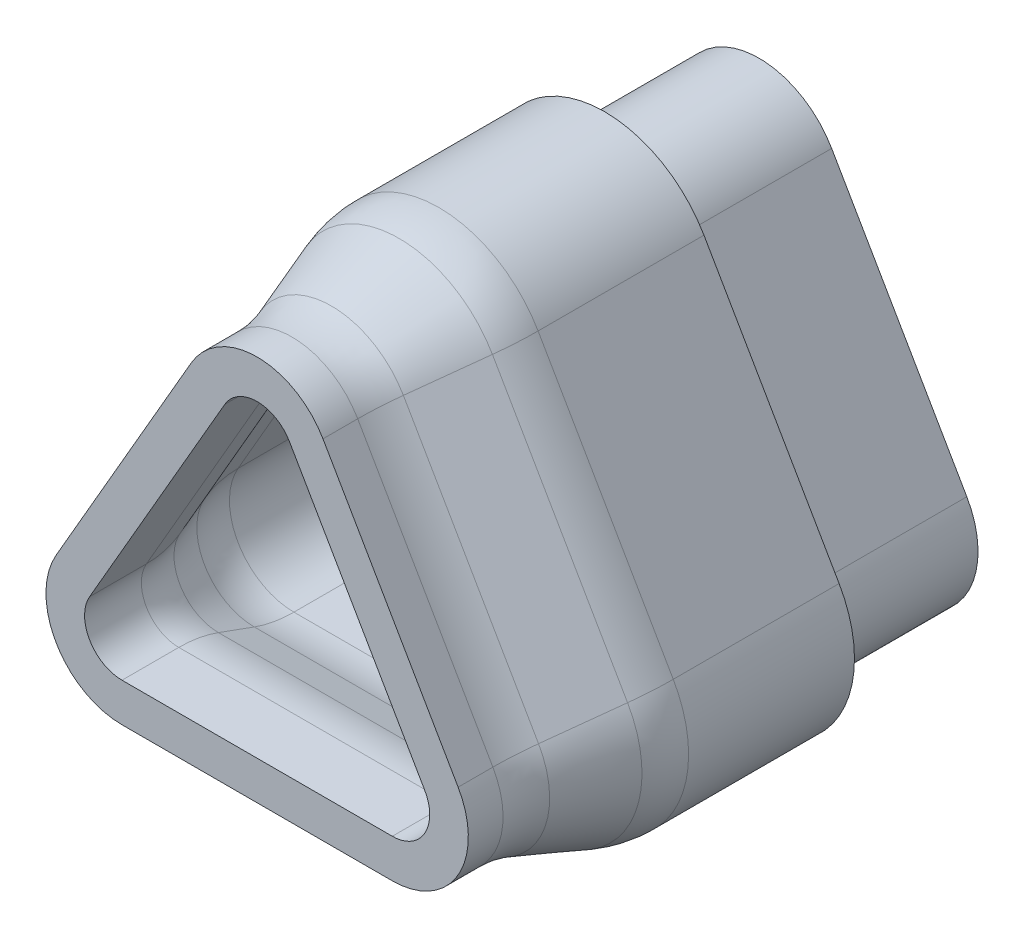
SolidWorks part; units mm, degrees
ref_plane "Спереди" through (0, 0, 0) normal (0, 0, 1) x (1, 0, 0)
ref_plane "Сверху" through (0, 0, 0) normal (0, 1, 0) x (1, 0, 0)
ref_plane "Справа" through (0, 0, 0) normal (1, 0, 0) x (0, 0, -1)
sketch "Эскиз2" plane through (0, 0, -4) normal (0, 0, 1) x (1, 0, 0)
  line L0 (-1.4453, 9.8655) -> (-4.9453, 3.8034)
  line L1 (-3.5, 1.3) -> (3.5, 1.3)
  line L2 (4.9453, 3.8034) -> (1.4453, 9.8655)
  line L3 (5.3783, 4.0534) -> (1.8783, 10.1155)
  line L4 (-1.8783, 10.1155) -> (-5.3783, 4.0534)
  line L5 (-3.5, 0.8) -> (3.5, 0.8)
  line L6 (5.3783, 4.0534) -> (1.8783, 10.1155)
  line L7 (-1.8783, 10.1155) -> (-5.3783, 4.0534)
  line L8 (-3.5, 0.8) -> (3.5, 0.8)
  arc A0 (1.4453, 9.8655) -> (-1.4453, 9.8655) centre (0, 9.0311) ccw
  arc A1 (-4.9453, 3.8034) -> (-3.5, 1.3) centre (-3.5, 2.9689) ccw
  arc A2 (3.5, 1.3) -> (4.9453, 3.8034) centre (3.5, 2.9689) ccw
  arc A3 (3.5, 0.8) -> (5.3783, 4.0534) centre (3.5, 2.9689) ccw
  arc A4 (1.8783, 10.1155) -> (-1.8783, 10.1155) centre (0, 9.0311) ccw
  arc A5 (-5.3783, 4.0534) -> (-3.5, 0.8) centre (-3.5, 2.9689) ccw
  arc A6 (3.5, 0.8) -> (5.3783, 4.0534) centre (3.5, 2.9689) ccw
  arc A7 (1.8783, 10.1155) -> (-1.8783, 10.1155) centre (0, 9.0311) ccw
  arc A8 (-5.3783, 4.0534) -> (-3.5, 0.8) centre (-3.5, 2.9689) ccw
  dimension "D1" = 0
  dimension "D2" = 0.5
extrude "Бобышка-Вытянуть1" add sketch "Эскиз2" along normal up to surface (4 mm away)
sketch "Эскиз3" plane through (0, 0, 0) normal (0, 0, 1) x (1, 0, 0)
  line L0 (4.9453, 3.8034) -> (1.4453, 9.8655) construction
  line L1 (-1.4453, 9.8655) -> (-4.9453, 3.8034) construction
  line L2 (-3.5, 1.3) -> (3.5, 1.3) construction
  line L3 (-3.5, 0) -> (3.5, 0)
  line L4 (6.0712, 4.4534) -> (2.5712, 10.5155)
  line L5 (-2.5712, 10.5155) -> (-6.0712, 4.4534)
  line L6 (-3.5, 0) -> (3.5, 0)
  line L7 (6.0712, 4.4534) -> (2.5712, 10.5155)
  line L8 (-2.5712, 10.5155) -> (-6.0712, 4.4534)
  line L9 (4.9453, 3.8034) -> (1.4453, 9.8655)
  line L10 (-1.4453, 9.8655) -> (-4.9453, 3.8034)
  line L11 (-3.5, 1.3) -> (3.5, 1.3)
  arc A0 (1.4453, 9.8655) -> (-1.4453, 9.8655) centre (0, 9.0311) ccw construction
  arc A1 (-4.9453, 3.8034) -> (-3.5, 1.3) centre (-3.5, 2.9689) ccw construction
  arc A2 (3.5, 1.3) -> (4.9453, 3.8034) centre (3.5, 2.9689) ccw construction
  arc A3 (3.5, 0) -> (6.0712, 4.4534) centre (3.5, 2.9689) ccw
  arc A4 (2.5712, 10.5155) -> (-2.5712, 10.5155) centre (0, 9.0311) ccw
  arc A5 (-6.0712, 4.4534) -> (-3.5, 0) centre (-3.5, 2.9689) ccw
  arc A6 (3.5, 0) -> (6.0712, 4.4534) centre (3.5, 2.9689) ccw
  arc A7 (2.5712, 10.5155) -> (-2.5712, 10.5155) centre (0, 9.0311) ccw
  arc A8 (-6.0712, 4.4534) -> (-3.5, 0) centre (-3.5, 2.9689) ccw
  arc A9 (1.4453, 9.8655) -> (-1.4453, 9.8655) centre (0, 9.0311) ccw
  arc A10 (-4.9453, 3.8034) -> (-3.5, 1.3) centre (-3.5, 2.9689) ccw
  arc A11 (3.5, 1.3) -> (4.9453, 3.8034) centre (3.5, 2.9689) ccw
  dimension "D1" = 0
extrude "Бобышка-Вытянуть2" add sketch "Эскиз3" along normal blind 4
sketch "Эскиз4" plane through (0, 0, 4) normal (0, 0, 1) x (1, 0, 0)
  line L12 (-1.7051, 10.0155) -> (-5.2051, 3.9534)
  line L13 (-3.5, 1) -> (3.5, 1)
  line L14 (5.2051, 3.9534) -> (1.7051, 10.0155)
  line L15 (-3.5, 2) -> (3.5, 2)
  line L16 (-0.8391, 9.5155) -> (-4.3391, 3.4534)
  line L17 (4.3391, 3.4534) -> (0.8391, 9.5155)
  line L18 (-3.5, 2) -> (3.5, 2)
  line L19 (-0.8391, 9.5155) -> (-4.3391, 3.4534)
  line L20 (4.3391, 3.4534) -> (0.8391, 9.5155)
  arc A9 (-5.2051, 3.9534) -> (-3.5, 1) centre (-3.5, 2.9689) ccw
  arc A10 (3.5, 1) -> (5.2051, 3.9534) centre (3.5, 2.9689) ccw
  arc A11 (1.7051, 10.0155) -> (-1.7051, 10.0155) centre (0, 9.0311) ccw
  arc A12 (3.5, 2) -> (4.3391, 3.4534) centre (3.5, 2.9689) ccw
  arc A13 (-4.3391, 3.4534) -> (-3.5, 2) centre (-3.5, 2.9689) ccw
  arc A14 (0.8391, 9.5155) -> (-0.8391, 9.5155) centre (0, 9.0311) ccw
  arc A15 (3.5, 2) -> (4.3391, 3.4534) centre (3.5, 2.9689) ccw
  arc A16 (-4.3391, 3.4534) -> (-3.5, 2) centre (-3.5, 2.9689) ccw
  arc A17 (0.8391, 9.5155) -> (-0.8391, 9.5155) centre (0, 9.0311) ccw
  dimension "D1" = 0.7
  dimension "D2" = 1
extrude "Бобышка-Вытянуть3" add sketch "Эскиз4" along normal blind 5
chamfer "Фаска1" distance 1.3 angle 70 6 edges at (0, 1, 4) (5.2051, 1.9845, 4) (-5.2051, 1.9845, 4) (3.4551, 6.9845, 4) (-3.4551, 6.9845, 4) (0, 11, 4) first distance on face at (0, 4.9896, 4)
chamfer "Фаска2" distance 3 angle 20 6 edges at (0, 2, 4) (4.3391, 2.4845, 4) (-4.3391, 2.4845, 4) (2.5891, 6.4845, 4) (-2.5891, 6.4845, 4) (0, 10, 4) first distance on face at (0, 2, 6.5) first distance on face at (4.1293, 2.6056, 6.5) first distance on face at (-4.1293, 2.6056, 6.5) first distance on face at (2.5891, 6.4845, 6.5) first distance on face at (-2.5891, 6.4845, 6.5) first distance on face at (0, 9.7578, 6.5)
fillet "Скругление1" radius 3 24 edges at (-2.5891, 6.4845, 7) (-4.3391, 2.4845, 7) (0, 2, 7) (4.3391, 2.4845, 7) (2.5891, 6.4845, 7) (3.1953, 6.8345, 5.0768) (4.9453, 2.1345, 5.0768) (0, 1.3, 5.0768) (-4.9453, 2.1345, 5.0768) (-3.1953, 6.8345, 5.0768) (3.4551, 6.9845, 7.5717) (5.2051, 1.9845, 7.5717) (0, 1, 7.5717) (-5.2051, 1.9845, 7.5717) (-3.4551, 6.9845, 7.5717) (-4.3212, 7.4845, 4.8242) (-6.0712, 1.4845, 4.8242) (0, 0, 4.8242) (6.0712, 1.4845, 4.8242) (4.3212, 7.4845, 4.8242) (0, 10, 7) (0, 10.7, 5.0768) (0, 11, 7.5717) (0, 12, 4.8242)
sketch "Эскиз5" plane through (-5.7889, 3.3422, 0) normal (-0.866, 0.5, 0) x (0, 0, 1)
  line L1 (-2, 5.8212) -> (-1, 5.8212)
  line L2 (-2, 5.8212) -> (-2, 2.8212)
  line L3 (-2, 2.8212) -> (-1, 2.8212)
  line L4 (-1, 5.8212) -> (-1, 2.8212)
extrude "Бобышка-Вытянуть4" add sketch "Эскиз5" along normal blind 0.6
chamfer "Фаска3" distance 0.6 angle 50 1 edges at (-4.1479, 7.3845, -2) first distance on face at (-3.8881, 7.2345, -2)
